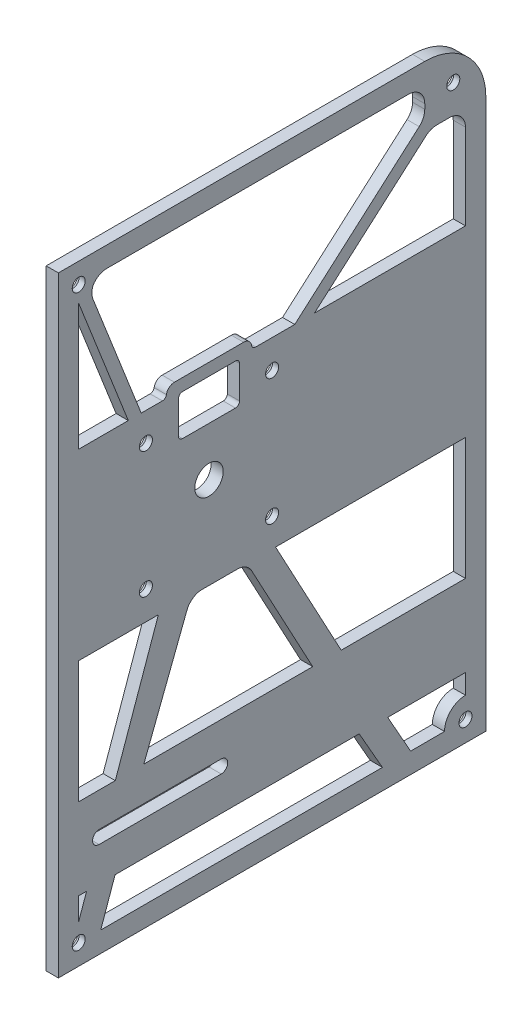
SolidWorks part; units mm, degrees
ref_plane "Front Plane" through (0, 0, 0) normal (0, 0, 1) x (1, 0, 0)
ref_plane "Top Plane" through (0, 0, 0) normal (0, 1, 0) x (1, 0, 0)
ref_plane "Right Plane" through (0, 0, 0) normal (1, 0, 0) x (0, 0, -1)
sketch "Sketch2" plane through (0, 0, 0) normal (1, 0, 0) x (0, 0, -1)
  line L0 (5, 9.5361) -> (5, 15)
  line L1 (0, 0) -> (105, 0)
  line L2 (0, 0) -> (0, 150)
  line L3 (0, 150) -> (90, 150)
  line L4 (105, 0) -> (105, 135)
  line L5 (9, 145) -> (90, 145)
  line L7 (10.4, 5) -> (79.6, 5)
  line L8 (90, 135) -> (105.4124, 150.4124) construction
  line L9 (90, 135) -> (111.5809, 135) construction
  line L11 (5, 145) -> (90, 145) construction
  line L12 (5, 5) -> (5, 145) construction
  line L13 (5, 5) -> (100, 5) construction
  line L14 (100, 5) -> (100, 135) construction
  line L17 (10, 25) -> (40, 25) construction
  line L18 (5, 15) -> (6.9273, 15)
  line L20 (5, 35) -> (13.9818, 35)
  line L22 (10, 26.6) -> (40, 26.6)
  line L23 (10, 23.4) -> (40, 23.4)
  line L24 (5, 35) -> (5, 65)
  line L25 (100, 35) -> (100, 65)
  line L26 (5, 110) -> (5, 141)
  line L27 (5, 110) -> (17.1786, 110)
  line L29 (5, 65) -> (24.5636, 65)
  line L31 (21.5, 72) -> (52.5, 72) construction
  line L32 (21.5, 72) -> (21.5, 103) construction
  line L33 (21.5, 103) -> (52.5, 103) construction
  line L34 (52.5, 72) -> (52.5, 103) construction
  line L35 (21.5, 72) -> (52.5, 103) construction
  line L36 (21.5, 103) -> (52.5, 72) construction
  line L37 (100, 110) -> (100, 135)
  line L44 (44.5, 99.5) -> (29.5, 99.5)
  line L48 (37, 87.5) -> (37, 115.858) construction
  line L49 (44.5, 99.5) -> (44.5, 109.5)
  line L50 (44.5, 109.5) -> (29.5, 109.5)
  line L51 (29.5, 99.5) -> (29.5, 109.5)
  line L52 (44.5, 99.5) -> (29.5, 109.5) construction
  line L53 (44.5, 109.5) -> (29.5, 99.5) construction
  line L54 (47.5, 112.5) -> (26.5, 112.5)
  line L55 (26.5, 110) -> (26.5, 112.5)
  line L57 (47.5, 110) -> (58.0596, 110)
  line L58 (47.5, 110) -> (47.5, 112.5)
  line L60 (47.5, 96.5) -> (47.5, 112.5) construction
  line L61 (26.5, 96.5) -> (26.5, 112.5) construction
  line L62 (47.5, 96.5) -> (26.5, 96.5) construction
  line L64 (24.5636, 65) -> (13.9818, 35)
  line L70 (73.8909, 15) -> (79.6, 5)
  line L71 (80.8909, 15) -> (86.5321, 5)
  line L72 (46.3455, 65) -> (62.4727, 35)
  line L73 (6.9273, 15) -> (5, 9.5361)
  line L74 (13.9273, 15) -> (10.4, 5)
  line L75 (32.5636, 65) -> (20.9818, 35)
  line L76 (53.3455, 65) -> (69.4727, 35)
  line L77 (13.9273, 15) -> (73.8909, 15)
  line L78 (53.3455, 65) -> (100, 65)
  line L79 (69.4727, 35) -> (100, 35)
  line L80 (20.9818, 35) -> (62.4727, 35)
  line L81 (32.5636, 65) -> (46.3455, 65)
  line L82 (80.8909, 15) -> (100, 15)
  line L83 (100, 10.1517) -> (100, 15)
  line L84 (94.8484, 5.0232) -> (86.5321, 5)
  line L85 (90, 145) -> (90, 137.9927)
  line L86 (91.438, 135) -> (100, 135)
  line L89 (17.1786, 110) -> (5, 141)
  line L90 (58.0596, 110) -> (90, 137.9927)
  line L91 (91.438, 135) -> (62.9141, 110)
  line L92 (20.35, 110) -> (7.7435, 142.0892)
  line L93 (62.9141, 110) -> (100, 110)
  line L95 (20.35, 110) -> (26.5, 110)
  arc A0 (90, 150) -> (105, 135) centre (90, 135) cw
  arc A1 (90, 145) -> (100, 135) centre (90, 135) cw construction
  circle A2 centre (5, 145) radius 1.6
  circle A3 centre (5, 5) radius 1.6
  circle A4 centre (100, 5) radius 1.6
  arc A6 (7.7435, 142.0892) -> (9, 145) centre (5, 145) ccw
  circle A11 centre (97, 142) radius 1.6
  arc A16 (10, 26.6) -> (10, 23.4) centre (10, 25) ccw
  arc A17 (40, 23.4) -> (40, 26.6) centre (40, 25) ccw
  circle A18 centre (21.5, 103) radius 1.6
  circle A19 centre (52.5, 103) radius 1.6
  circle A20 centre (52.5, 72) radius 1.6
  circle A21 centre (21.5, 72) radius 1.6
  circle A22 centre (37, 87.5) radius 3.5
  arc A23 (100, 10.1517) -> (94.8484, 5.0232) centre (100, 5) ccw
  point P34 (25, 25)
  point P43 (37, 87.5)
  point P52 (37, 104.5)
  dimension "D1" = 15
  dimension "D6" = 3.2
  dimension "D7" = 3.2
  dimension "D8" = 4
  dimension "D9" = 3.2
  dimension "D10" = 3.2
  dimension "D11" = 8
  dimension "D14" = 3.2
  dimension "D15" = 30
  dimension "D19" = 5
  dimension "D20" = 3.2
  dimension "D21" = 3.2
  dimension "D22" = 3.2
  dimension "D23" = 3.2
  dimension "D34" = 7
  dimension "D2" = 150
  dimension "D3" = 105
  dimension "D5" = 45
  dimension "D16" = 20
  dimension "D17" = 10
  dimension "D18" = 20
  dimension "D24" = 31
  dimension "D25" = 31
  dimension "D26" = 35
  dimension "D27" = 45
  dimension "D28" = 22.5
  dimension "D29" = 37
  dimension "D31" = 10
  dimension "D30" = 15
  dimension "D33" = 1.5
  dimension "D35" = 2.5
  dimension "D4" = 5
  dimension "D32" = 3
extrude "Boss-Extrude1" add sketch "Sketch2" along normal blind 3
chamfer "Chamfer1" distance 1.5 angle 45 8 edges at (0, 72, -23.1) (0, 72, -54.1) (0, 103, -23.1) (0, 103, -54.1) (0, 5, -6.6) (0, 5, -101.6) (0, 145, -6.6) (0, 142, -98.6)
fillet "Fillet1" radius 2 2 edges at (1.5, 112.5, -47.5) (1.5, 112.5, -26.5)
fillet "Fillet2" radius 1 6 edges at (1.5, 110, -47.5) (1.5, 109.5, -44.5) (1.5, 99.5, -44.5) (1.5, 99.5, -29.5) (1.5, 109.5, -29.5) (1.5, 110, -26.5)
fillet "Fillet3" radius 4 8 edges at (1.5, 145, -90) (1.5, 135, -100) (1.5, 65, -32.5636) (1.5, 65, -46.3455) (1.5, 145, -9) (1.5, 142.0892, -7.7435) (1.5, 137.9927, -90) (1.5, 135, -91.438)
